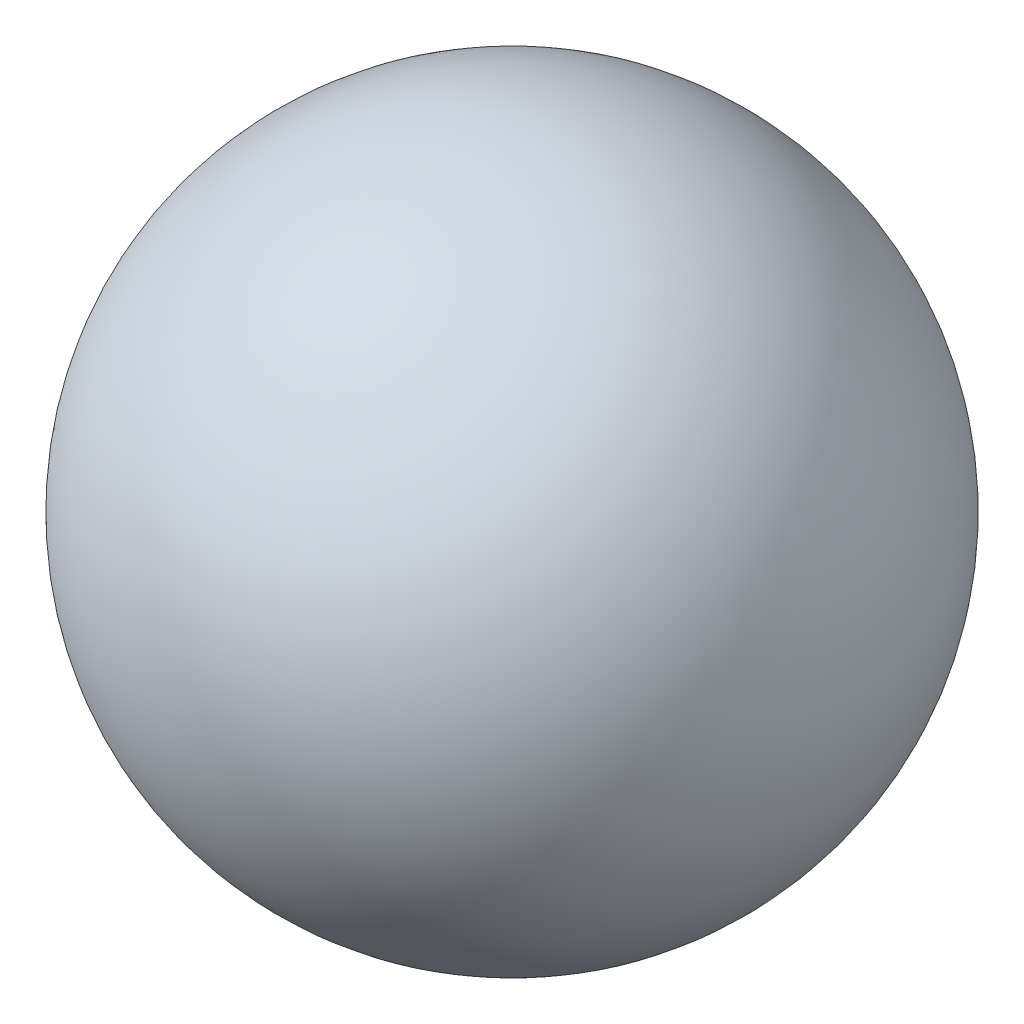
SolidWorks part; units mm, degrees
ref_plane "Front" through (0, 0, 0) normal (0, 0, 1) x (1, 0, 0)
ref_plane "Top" through (0, 0, 0) normal (0, 1, 0) x (1, 0, 0)
ref_plane "Right" through (0, 0, 0) normal (1, 0, 0) x (0, 0, -1)
sketch "Sketch1" plane through (0, 0, 0) normal (0, 0, 1) x (1, 0, 0)
  line L0 (0, 63) -> (0, 0) construction
  line L1 (0, 63) -> (0, 0)
  arc A0 (0, 63) -> (0, 0) centre (0, 31.5) cw
  point P2 (0, -15.5943)
  point P5 (0, 0)
  point P6 (11.4676, 30.6899)
  point P7 (0, 0)
  point P9 (0, -1.2422)
  dimension "D1" = 31.5
  dimension "D2" = 63
revolve "Revolve1" add sketch "Sketch1" angle 360 about L0
sketch "Sketch2" plane through (0, 0, 0) normal (0, 0, 1) x (1, 0, 0)
  point P0 (0, 0)
